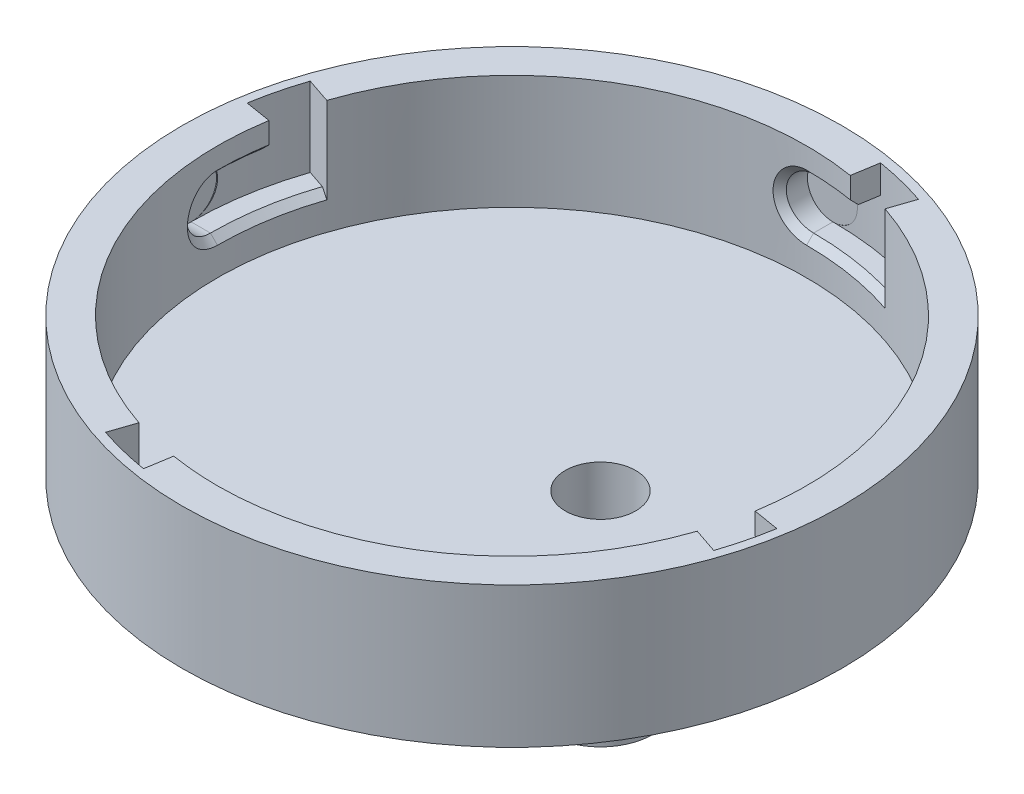
SolidWorks part; units mm, degrees
ref_plane "Front Plane" through (0, 0, 0) normal (0, 0, 1) x (1, 0, 0)
ref_plane "Top Plane" through (0, 0, 0) normal (0, 1, 0) x (1, 0, 0)
ref_plane "Right Plane" through (0, 0, 0) normal (1, 0, 0) x (0, 0, -1)
sketch "Sketch1" plane through (0, 0, 0) normal (0, 1, 0) x (1, 0, 0)
  circle A0 centre (0, 0) radius 16.75
  circle A1 centre (0, 0) radius 18.25
  circle A2 centre (0, 0) radius 18.75
  dimension "D1" = 33.5
  dimension "D2" = 1.5
  dimension "D3" = 0.5
extrude "Boss-Extrude1" add sketch "Sketch1" along normal blind 6.5 contours A1 A0 region at (-17.7338, 0, 0)
extrude "Boss-Extrude2" add sketch "Sketch1<6>" against normal blind 1.5 contours A0 | A1 A0 region at (0, 0, 0) region at (-17.7338, 0, 0)
sketch "Sketch1<6>" plane through (0, 0, 0) normal (0, 1, 0) x (1, 0, 0) same geometry as "Sketch1"
ref_plane "Plane1" through (16.75, 0, 0) normal (-1, 0, 0) x (0, 0, 1)
sketch "Sketch3" plane through (16.75, 0, 0) normal (-1, 0, 0) x (0, 0, 1)
  line L0 (0, 0) -> (0, 6.5) construction
  line L3 (0, 4.9) -> (3.55, 4.9)
  line L4 (0, 3.45) -> (5, 3.45) construction
  line L5 (3.55, 4.9) -> (6.45, 2) construction
  line L6 (0, 2) -> (6.45, 2)
  line L7 (3.55, 4.9) -> (3.55, 6.5)
  line L8 (6.45, 2) -> (6.45, 6.5)
  line L9 (18.25, 6.5) -> (-18.25, 6.5) construction
  line L11 (16.75, 6.5) -> (-16.75, 6.5) construction
  line L12 (3.55, 6.5) -> (6.45, 6.5)
  circle A0 centre (0, 3.25) radius 1.25 construction
  circle A1 centre (0, 3.45) radius 1.45
  point P3 (0, 0)
  point P4 (0, 5.7779)
  point P18 (1.45, 3.45)
  dimension "D1" = 2.5
  dimension "D4" = 2.9
  dimension "D2" = 3.25
  dimension "D3" = 0.2
  dimension "D5" = 135
  dimension "D6" = 5
extrude "Cut-Extrude1" cut sketch "Sketch3" against normal blind 1.5 and the other way blind 1.5 contours A1 region at (16.75, 3.45, 0)
ref_axis "Axis1" through (16.605, 3.45, 0) along (1, 0, 0)
ref_plane "Plane4" through (0, 3.45, 0) normal (0, 1, 0) x (1, 0, 0)
sketch "Sketch5" plane through (0, 3.45, 0) normal (0, 1, 0) x (1, 0, 0)
  line L0 (18.25, 0) -> (0, 0)
  line L1 (0, 0) -> (18.0102, -2.9485)
  line L3 (16.605, 0) -> (18.25, 0) construction
  line L4 (17.2968, -5.821) -> (0, 0)
  line L5 (18.0102, -2.9485) -> (0, 0)
  arc A0 (18.25, 0) -> (18.0102, -2.9485) centre (0, 0) cw
  arc A1 (18.1923, -1.45) -> (18.1923, 1.45) centre (0, 0) ccw construction
  circle A2 centre (0, 0) radius 18.25 construction
  arc A3 (18.0102, -2.9485) -> (17.2968, -5.821) centre (0, 0) cw
  point P13 (17.552, -5.1784)
  point P14 (18.0596, -2.2818)
  point P15 (0, 0)
  dimension "D1" = 9.302
  dimension "D2" = 18.6
ref_plane "Plane5" through (0, 2, 0) normal (0, 1, 0) x (1, 0, 0)
ref_plane "Plane6" through (0, 4.9, 0) normal (0, -1, 0) x (-1, 0, 0)
extrude "Cut-Extrude2" cut sketch "Sketch5" against normal up to surface (1.45 mm away) and the other way up to surface (1.45 mm away) contours A0 L0 L5 | A0 L5 L1 region at (12.1133, 3.45, 0.985) up to plane "Plane5" other way up to plane "Plane6"
extrude "Cut-Extrude3" cut sketch "Sketch5<4>" against normal up to surface (1.45 mm away) and the other way through all contours A3 L1 L4 region at (11.7949, 3.45, 2.9296) up to plane "Plane5"
sketch "Sketch5<4>" plane through (0, 3.45, 0) normal (0, 1, 0) x (1, 0, 0) same geometry as "Sketch5"
extrude "Boss-Extrude3" add sketch "Sketch1<8>" along normal up to surface (6.5 mm away) contours A2 A1 region at (-18.697, 0, 0) up to face at (-0.028, 6.5, -0.0069)
sketch "Sketch1<8>" plane through (0, 0, 0) normal (0, 1, 0) x (1, 0, 0) same geometry as "Sketch1"
extrude "Boss-Extrude4" add sketch "Sketch1<10>" against normal up to surface (1.5 mm away) contours A2 A1 region at (-18.697, 0, 0) up to face at (0, -1.5, 18.25)
sketch "Sketch1<10>" plane through (0, 0, 0) normal (0, 1, 0) x (1, 0, 0) same geometry as "Sketch1"
chamfer "Chamfer1" distance 0.4 angle 45 3 edges at (16.5298, 2, 2.7069) (16.6879, 3.6076, 1.4414) (16.6949, 4.9, 1.3576)
pattern_circular "CirPattern1" count 4 over 360 about axis through (0, 6.5, 0) along (0, 1, 0) of "Cut-Extrude2", "Cut-Extrude1", "Chamfer1", "Cut-Extrude3"
sketch "Sketch6" plane through (0, 0, 0) normal (0, 1, 0) x (1, 0, 0)
  line L0 (16.75, 0) -> (-16.75, 0) construction
  line L1 (-16.7452, 0.4) -> (16.7452, 0.4) construction
  line L2 (13.24, 0) -> (7.42, 0)
  arc A0 (16.5299, -2.7062) -> (5.3426, 15.8751) centre (0, 0) ccw construction
  circle A1 centre (0, 0) radius 16.75 construction
  circle A2 centre (4.63, 0.4) radius 2
  point P8 (13.24, 0)
  point P9 (7.42, 0)
  point P10 (-6.63, 0)
  point P11 (-13.25, 0)
  point P19 (10.33, 0)
  dimension "D6" = 4
  dimension "D1" = 14.05
  dimension "D2" = 6.63
  dimension "D3" = 6.62
  dimension "D4" = 5.82
  dimension "D5" = 0.4
  dimension "D7" = 5.7
extrude "Cut-Extrude4" cut sketch "Sketch6" against normal through all contours A2 region at (4.63, 0, -0.4)
sketch "Sketch7" plane through (0, -1.5, 0) normal (0, -1, 0) x (1, 0, 0)
  line L0 (6.63, -0.4) -> (2.63, -0.4)
  line L1 (4.63, -0.4) -> (3.13, -2.9981)
  line L2 (4.63, -0.4) -> (3.13, 2.1981)
  circle A0 centre (4.63, -0.4) radius 2 construction
  circle A1 centre (4.63, -0.4) radius 2
  circle A2 centre (4.63, -0.4) radius 3
  circle M5 centre (4.63, -0.4) radius 2
  dimension "D1" = 1
  dimension "D2" = 60
  dimension "D3" = 60
extrude "Boss-Extrude5" add sketch "Sketch7" along normal blind 9 contours L1 A2 L2 M5 region at (5.6675, -1.5, 1.397)
extrude "Boss-Extrude6" add sketch "Sketch7<3>" along normal blind 4 contours L2 A2 L1 M5 region at (2.535, -1.5, -0.4)
sketch "Sketch7<3>" plane through (0, -1.5, 0) normal (0, -1, 0) x (1, 0, 0) same geometry as "Sketch7"
chamfer "Chamfer2" distance 1 angle 45 2 edges at (3.38, -10.5, 1.7651) (3.38, -10.5, -2.5651)
fillet "Fillet2" radius 0.8 1 edges at (2.63, -5.5, -0.4)
equation "\"D4@Sketch3\"= \"D3@Sketch3\" * 2 + 2.5"
